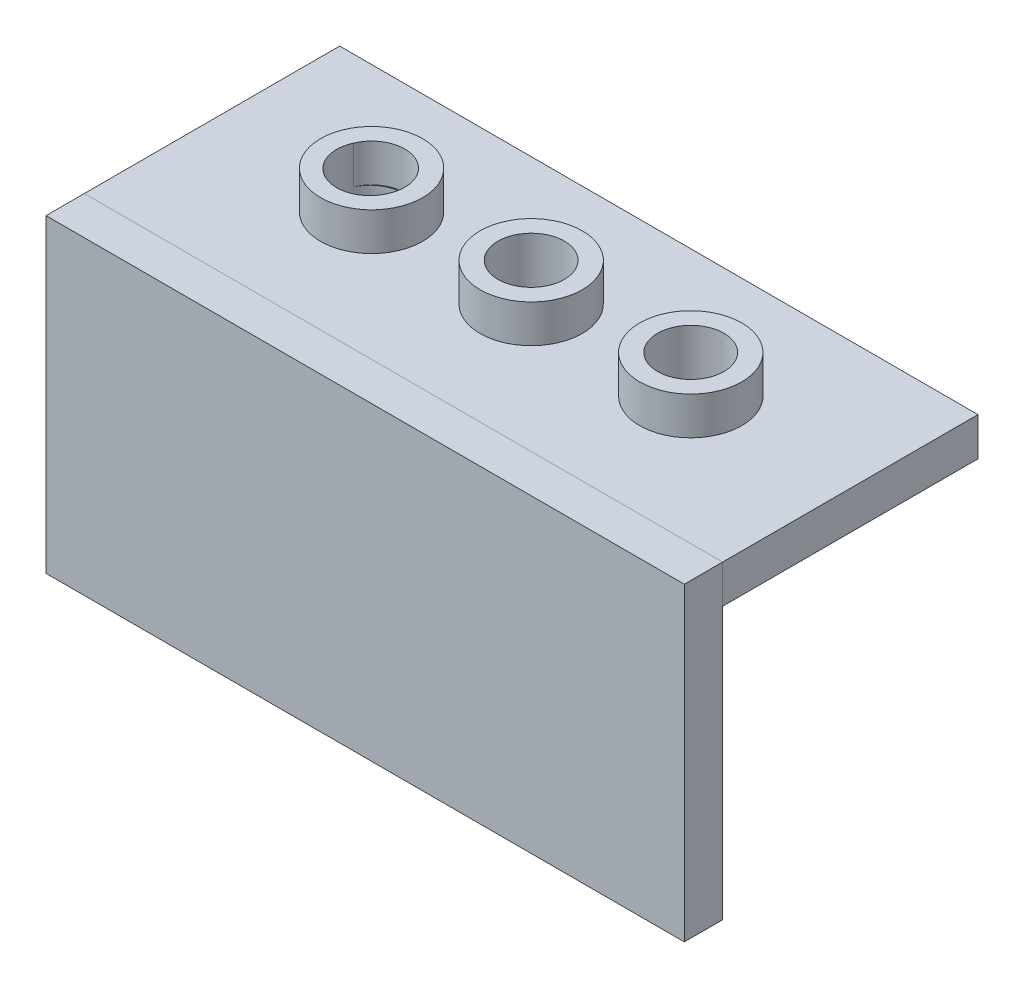
SolidWorks part; units mm, degrees
ref_plane "Front Plane" through (0, 0, 0) normal (0, 0, 1) x (1, 0, 0)
ref_plane "Top Plane" through (0, 0, 0) normal (0, 1, 0) x (1, 0, 0)
ref_plane "Right Plane" through (0, 0, 0) normal (1, 0, 0) x (0, 0, -1)
sketch "Sketch1" plane through (0, 0, 0) normal (0, 1, 0) x (1, 0, 0)
  line L1 (-25, -10) -> (25, -10)
  line L2 (-25, -10) -> (-25, 10)
  line L3 (-25, 10) -> (25, 10)
  line L4 (25, -10) -> (25, 10)
  line L5 (-25, -10) -> (25, 10) construction
  line L6 (-25, 10) -> (25, -10) construction
  point P0 (0, 0)
extrude "Boss-Extrude2" add sketch "Sketch1" along normal blind 3
sketch "Sketch3" plane through (0, 3, 0) normal (0, 1, 0) x (1, 0, 0)
  circle A0 centre (0, 0) radius 4
  circle A1 centre (-12.5, 0) radius 4
  circle A2 centre (12.5, 0) radius 4
extrude "Boss-Extrude3" add sketch "Sketch3" along normal blind 6.27
sketch "Sketch4" plane through (0, 9.27, 0) normal (0, 1, 0) x (1, 0, 0)
  circle A0 centre (0, 0) radius 2.6
  circle A1 centre (-12.5, 0) radius 2.6
  circle A2 centre (12.5, 0) radius 2.6
extrude "Cut-Extrude1" cut sketch "Sketch4" against normal through all both and the other way through all
sketch "Sketch5" plane through (-25, 0, 0) normal (-1, 0, 0) x (0, 0, 1)
  line L0 (10, 3) -> (10, 5.3)
  line L1 (10, 3) -> (-10, 3)
  line L2 (-10, 3) -> (-10, 5.3)
  line L3 (-10, 5.3) -> (10, 5.3)
extrude "Boss-Extrude4" add sketch "Sketch5" against normal blind 50
sketch "Sketch6" plane through (-25, 0, 0) normal (-1, 0, 0) x (0, 0, 1)
  line L0 (-10, 0) -> (-10, 2.65)
  line L1 (-10, 5.3) -> (-10, 0) construction
  line L2 (-10, 2.65) -> (10, 2.65)
  line L3 (10, 5.3) -> (10, 0) construction
  line L4 (10, 2.65) -> (10, 0)
  line L5 (10, 0) -> (-10, 0)
extrude "Cut-Extrude2" cut sketch "Sketch6" against normal through all both and the other way through all
sketch "Sketch7" plane through (0, 2.65, 0) normal (0, -1, 0) x (1, 0, 0)
  circle A0 centre (-12.5, 0) radius 2.6
  circle A1 centre (0, 0) radius 2.6
  circle A2 centre (12.5, 0) radius 2.6
extrude "Cut-Extrude3" cut sketch "Sketch7" against normal through all both and the other way through all
sketch "Sketch8" plane through (-25, 0, 0) normal (-1, 0, 0) x (0, 0, 1)
  line L0 (-10, 5.3) -> (-10, 6.3)
  line L1 (-10, 6.3) -> (10.0042, 6.3)
  line L2 (10.0042, 6.3) -> (10, 2.65)
  line L3 (10, 2.65) -> (-10, 2.65)
  line L4 (-10, 2.65) -> (-10, 6.3)
  line M5 (-10, 5.3) -> (-10, 2.65)
  line M6 (-10, 2.65) -> (10, 2.65)
  line M7 (10, 2.65) -> (10, 5.3)
  line M8 (10, 5.3) -> (-10, 5.3)
extrude "Boss-Extrude5" add sketch "Sketch8" against normal blind 50 contours L2 L1 L0 M8 M7 | M8 M5 M6 M7 region at (-25, 3.975, 0) region at (-25, 5.7997, 0.0038)
sketch "Sketch10" plane through (0, 6.3, 0) normal (0, 1, 0) x (1, 0, 0)
  circle A0 centre (12.5, 0) radius 2.6
  circle A1 centre (0, 0) radius 2.6
  circle A2 centre (-12.5425, -0.0968) radius 2.6
extrude "Cut-Extrude4" cut sketch "Sketch10" against normal through all both and the other way through all
sketch "Sketch11" plane through (-25, 0, 0) normal (-1, 0, 0) x (0, 0, 1)
  line L0 (10, 2.65) -> (10.0007, 3.3)
  line L1 (10.0042, 6.3) -> (10, 2.65) construction
  line L2 (10.0007, 3.3) -> (-10, 3.3)
  line L3 (-10, 6.3) -> (-10, 2.65) construction
  line L4 (-10, 3.3) -> (-10, 2.65)
  line L5 (-10, 2.65) -> (10, 2.65)
extrude "Cut-Extrude5" cut sketch "Sketch11" against normal through all both and the other way through all
sketch "Sketch12" plane through (-25, 0, 0) normal (-1, 0, 0) x (0, 0, 1)
  line L0 (10.0042, 6.3) -> (13.0042, 6.3)
  line L1 (13.0042, 6.3) -> (13.0042, -17.9693)
  line L2 (13.0042, -17.9693) -> (10.0007, -17.9693)
  line L3 (10.0007, -17.9693) -> (10.0042, 6.3)
extrude "Boss-Extrude6" add sketch "Sketch12" against normal blind 50 separate body
